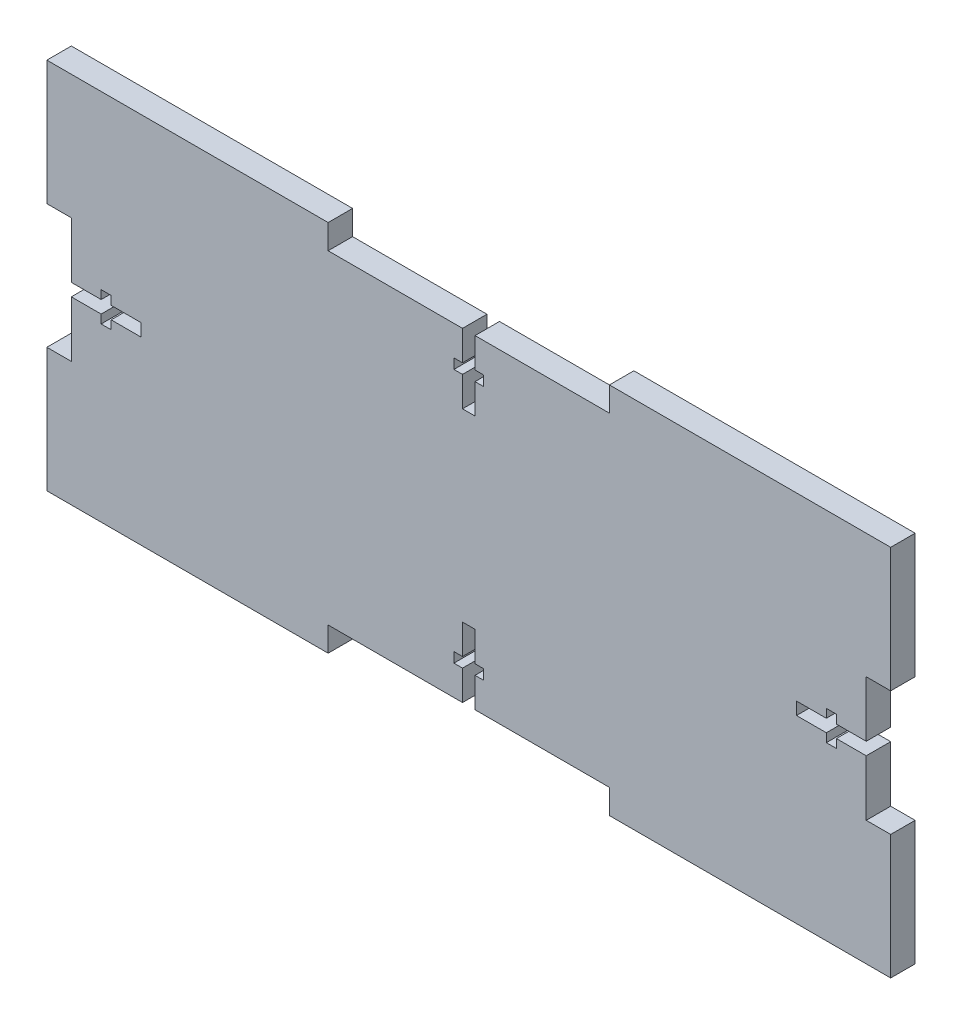
SolidWorks part; units mm, degrees
ref_plane "Front Plane" through (0, 0, 0) normal (0, 0, 1) x (1, 0, 0)
ref_plane "Top Plane" through (0, 0, 0) normal (0, 1, 0) x (1, 0, 0)
ref_plane "Right Plane" through (0, 0, 0) normal (1, 0, 0) x (0, 0, -1)
sketch "Sketch1" plane through (0, 0, 0) normal (0, 0, 1) x (1, 0, 0)
  line L1 (-87.63, -38.735) -> (87.63, -38.735)
  line L2 (-87.63, -38.735) -> (-87.63, 38.735)
  line L3 (-87.63, 38.735) -> (87.63, 38.735)
  line L4 (87.63, -38.735) -> (87.63, 38.735)
  line L5 (-87.63, -38.735) -> (87.63, 38.735) construction
  line L6 (-87.63, 38.735) -> (87.63, -38.735) construction
  point P0 (0, 0)
  dimension "D1" = 175.26
  dimension "D2" = 77.47
extrude "Boss-Extrude1" add sketch "Sketch1" along normal blind 5.08
sketch "Sketch2" plane through (0, 0, 5.08) normal (0, 0, 1) x (1, 0, 0)
  line L0 (29.21, -38.735) -> (29.21, -33.655)
  line L1 (-29.21, 38.735) -> (29.21, 38.735)
  line L2 (-29.21, 38.735) -> (-29.21, 33.655)
  line L3 (-29.21, 33.655) -> (29.21, 33.655)
  line L4 (29.21, 38.735) -> (29.21, 33.655)
  line L5 (87.63, 38.735) -> (-87.63, 38.735) construction
  line L6 (0, 0) -> (87.63, 0) construction
  line L7 (87.63, -38.735) -> (87.63, 38.735) construction
  line L8 (-29.21, -38.735) -> (29.21, -38.735)
  line L9 (-29.21, -38.735) -> (-29.21, -33.655)
  line L10 (-29.21, -33.655) -> (29.21, -33.655)
  dimension "D1" = 58.42
  dimension "D2" = 5.08
  dimension "D3" = 58.42
extrude "Cut-Extrude1" cut sketch "Sketch2" against normal through all
sketch "Sketch3" plane through (0, 0, 5.08) normal (0, 0, 1) x (1, 0, 0)
  line L0 (-87.63, 38.735) -> (-87.63, -38.735) construction
  line L1 (-87.63, 12.9117) -> (-82.55, 12.9117)
  line L2 (-87.63, 12.9117) -> (-87.63, -12.9117)
  line L3 (-87.63, -12.9117) -> (-82.55, -12.9117)
  line L4 (-82.55, 12.9117) -> (-82.55, -12.9117)
  line L5 (0, 0) -> (0, 39.951) construction
  line L6 (87.63, -12.9117) -> (82.55, -12.9117)
  line L7 (87.63, 12.9117) -> (87.63, -12.9117)
  line L8 (87.63, 12.9117) -> (82.55, 12.9117)
  line L9 (82.55, 12.9117) -> (82.55, -12.9117)
  dimension "D1" = 5.08
  dimension "D2" = 25.8233
  dimension "D3" = 25.8233
extrude "Cut-Extrude2" cut sketch "Sketch3" against normal through all
sketch "Sketch4" plane through (0, 0, 5.08) normal (0, 0, 1) x (1, 0, 0)
  line L0 (0, 0) -> (-82.55, 0) construction
  line L1 (-82.55, -12.9117) -> (-82.55, 12.9117) construction
  line L2 (0, 0) -> (0, 28.5152) construction
  line L3 (-82.55, 1.3017) -> (-68.072, 1.3017)
  line L4 (-82.55, 1.3017) -> (-82.55, -1.3018)
  line L5 (-82.55, -1.3018) -> (-68.072, -1.3018)
  line L6 (-68.072, 1.3017) -> (-68.072, -1.3018)
  line L7 (68.072, 1.3017) -> (68.072, -1.3017)
  line L8 (82.55, -1.3017) -> (68.072, -1.3017)
  line L9 (82.55, 1.3017) -> (82.55, -1.3017)
  line L10 (82.55, 1.3017) -> (68.072, 1.3017)
  point P9 (-68.072, 0)
  dimension "D1" = 1.3017
  dimension "D2" = 14.478
extrude "Cut-Extrude3" cut sketch "Sketch4" against normal through all
sketch "Sketch5" plane through (0, 0, 5.08) normal (0, 0, 1) x (1, 0, 0)
  line L0 (0, 0) -> (0, 33.655) construction
  line L1 (-29.21, 33.655) -> (29.21, 33.655) construction
  line L2 (0, 0) -> (35.9654, 0) construction
  line L3 (-1.3017, 33.655) -> (1.3017, 33.655)
  line L4 (-1.3017, 33.655) -> (-1.3017, 19.177)
  line L5 (-1.3017, 19.177) -> (1.3018, 19.177)
  line L6 (1.3017, 33.655) -> (1.3018, 19.177)
  line L7 (-1.3017, -33.655) -> (1.3017, -33.655)
  line L8 (-1.3017, -33.655) -> (-1.3017, -19.177)
  line L9 (-1.3017, -19.177) -> (1.3018, -19.177)
  line L10 (1.3017, -33.655) -> (1.3018, -19.177)
  dimension "D1" = 1.3017
  dimension "D2" = 1.3017
  dimension "D3" = 14.478
extrude "Cut-Extrude4" cut sketch "Sketch5" against normal through all
sketch "Sketch6" plane through (0, 0, 5.08) normal (0, 0, 1) x (1, 0, 0)
  line L0 (-75.311, 1.3018) -> (-75.311, -1.3018) construction
  line L1 (-68.072, 1.3017) -> (-82.55, 1.3017) construction
  line L2 (-82.55, -1.3018) -> (-68.072, -1.3018) construction
  line L3 (-1.3017, 26.416) -> (1.3017, 26.416) construction
  line L4 (-1.3017, 33.655) -> (-1.3017, 19.177) construction
  line L5 (1.3018, 19.177) -> (1.3017, 33.655) construction
  line L6 (-1.3017, 26.416) -> (-3.0861, 26.416) construction
  line L7 (-3.0861, 27.4574) -> (3.0861, 27.4574)
  line L8 (-3.0861, 27.4574) -> (-3.0861, 25.3746)
  line L9 (-3.0861, 25.3746) -> (3.0861, 25.3746)
  line L10 (3.0861, 27.4574) -> (3.0861, 25.3746)
  line L11 (0, 0) -> (19.2929, 0) construction
  line L12 (0, 0) -> (0, 14.5303) construction
  line L13 (-3.0861, -25.3746) -> (3.0861, -25.3746)
  line L14 (-3.0861, -27.4574) -> (-3.0861, -25.3746)
  line L15 (-3.0861, -27.4574) -> (3.0861, -27.4574)
  line L16 (3.0861, -27.4574) -> (3.0861, -25.3746)
  line L17 (-75.311, -1.3018) -> (-75.311, -3.0861) construction
  line L18 (-76.3524, 3.0861) -> (-74.2696, 3.0861)
  line L19 (-76.3524, 3.0861) -> (-76.3524, -3.0861)
  line L20 (-76.3524, -3.0861) -> (-74.2696, -3.0861)
  line L21 (-74.2696, 3.0861) -> (-74.2696, -3.0861)
  line L22 (0, 19.177) -> (0, 25.3746) construction
  line L23 (-1.3017, 19.177) -> (1.3018, 19.177) construction
  line L24 (-68.072, 0) -> (-74.2696, 0) construction
  line L25 (-68.072, -1.3018) -> (-68.072, 1.3017) construction
  line L26 (76.3524, -3.0861) -> (74.2696, -3.0861)
  line L27 (74.2696, 3.0861) -> (74.2696, -3.0861)
  line L28 (76.3524, 3.0861) -> (76.3524, -3.0861)
  line L29 (76.3524, 3.0861) -> (74.2696, 3.0861)
  dimension "D1" = 6.1722
  dimension "D2" = 2.0828
  dimension "D3" = 2.0828
  dimension "D4" = 6.1722
extrude "Cut-Extrude5" cut sketch "Sketch6" against normal through all
equation "\"Length\"= \"Length@Box.SLDASM\""
equation "\"D1@Sketch1\"  = \"Length\" + 2 * \"Material\""
equation "\"Width\"= \"Height@Box.SLDASM\""
equation "\"D2@Sketch1\" = \"Width\" + 2 * \"Material\""
equation "\"Material\"= \"Material@Box.SLDASM\""
equation "\"D1@Boss-Extrude1\" = \"Material\""
equation "\"D1@Sketch2\"=(\"Length\" +\"Material\"*2)/3"
equation "\"D2@Sketch2\"= \"Material\""
equation "\"D3@Sketch2\"=(\"Length\" +\"Material\"*2)/3"
equation "\"D1@Sketch3\"=\"Material\""
equation "\"D2@Sketch3\"=(\"Width\" +\"Material\"*2)/3"
equation "\"D3@Sketch3\"=(\"Width\" +\"Material\"*2)/3"
equation "\"Diameter of Screw\"= \"Diameter of Screw@Box.SLDASM\""
equation "\"Length of screw\"= \"Length of Screw@Box.SLDASM\""
equation "\"D3@Sketch5\"= \"Length of screw\" - \"Material\""
equation "\"D2@Sketch5\"=\"Diameter of Screw\"/2"
equation "\"D1@Sketch5\"= \"Diameter of Screw\" /2"
equation "\"D1@Sketch4\"= \"Diameter of Screw\" /2"
equation "\"D2@Sketch4\"= \"Length of screw\" - \"Material\""
equation "\"Diameter of Nut\"= \"Diameter of Nut@Box.SLDASM\""
equation "\"D1@Sketch6\"=\"Diameter of Nut\""
equation "\"Height of Nut\"= \"Height of Nut@Box.SLDASM\""
equation "\"D3@Sketch6\"= \"Height of Nut\""
equation "\"D4@Sketch6\"=\"Diameter of Nut\""
equation "\"D2@Sketch6\"=\"Height of Nut\""
